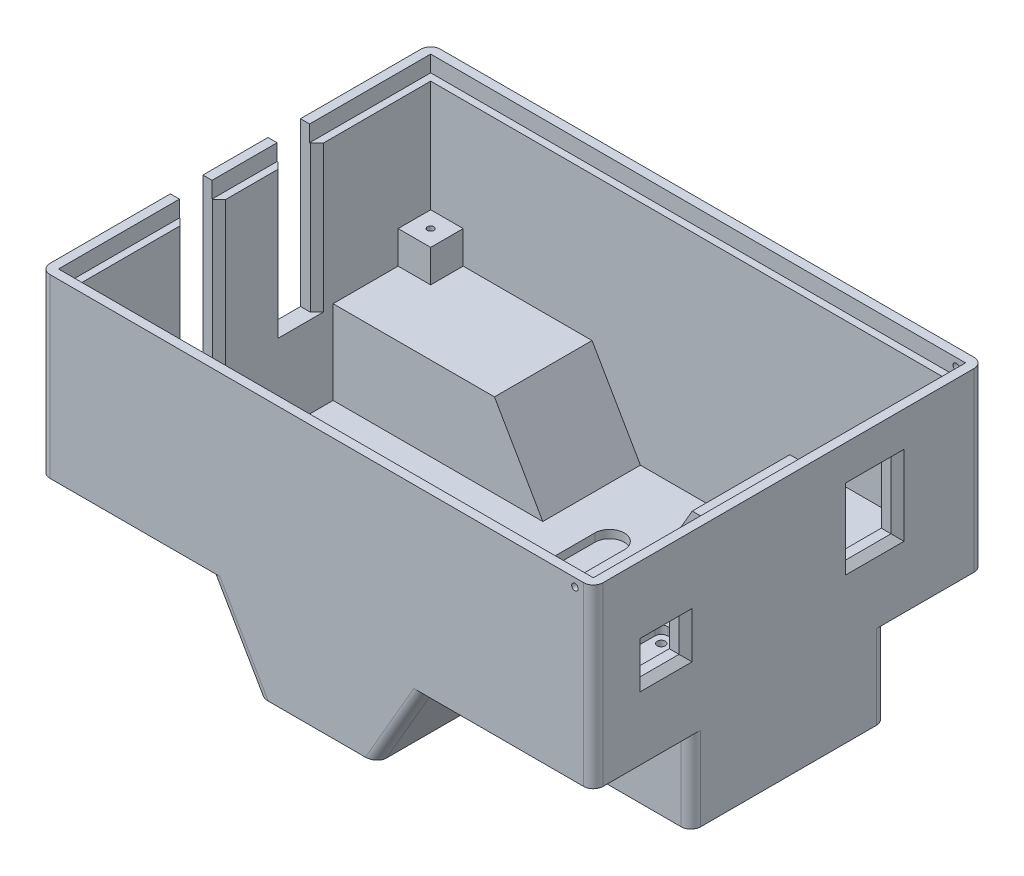
SolidWorks part; units mm, degrees
ref_plane "Plano frontal" through (0, 0, 0) normal (0, 0, 1) x (1, 0, 0)
ref_plane "Plano superior" through (0, 0, 0) normal (0, 1, 0) x (1, 0, 0)
ref_plane "Plano direito" through (0, 0, 0) normal (1, 0, 0) x (0, 0, -1)
sketch "Esboço7" plane through (0, 0, 0) normal (0, 1, 0) x (1, 0, 0)
  line L1 (85, -60) -> (-85, -60)
  line L2 (85, -60) -> (85, 60)
  line L3 (85, 60) -> (-85, 60)
  line L4 (-85, -60) -> (-85, 60)
  line L5 (85, -60) -> (-85, 60) construction
  line L6 (85, 60) -> (-85, -60) construction
  point P0 (0, 0)
  dimension "D1" = 120
  dimension "D2" = 170
extrude "Ressalto-extrusão4" add sketch "Esboço7" along normal blind 80 contours L4 L1 L2 L3 region at (0, 0, 0)
sketch "Esboço17" plane through (0, 0, 60) normal (0, 0, 1) x (1, 0, 0)
  line L0 (-85, 25.75) -> (-33.2819, 25.75)
  line L1 (-85, 80) -> (-85, 0) construction
  line L2 (-33.2819, 25.75) -> (-18.4152, 0)
  line L3 (85, 0) -> (-85, 0) construction
  line L4 (0, 0) -> (0, 80) construction
  line L5 (85, 80) -> (-85, 80) construction
  line L6 (-85, 25.75) -> (-85, 0)
  line L7 (-85, 0) -> (-18.4152, 0)
  line L8 (85, 0) -> (18.4152, 0)
  line L9 (85, 25.75) -> (85, 0)
  line L10 (85, 25.75) -> (33.2819, 25.75)
  line L11 (33.2819, 25.75) -> (18.4152, 0)
  line L12 (-53.5, 22.75) -> (-53.5, 25.75) construction
  line L13 (-18.4152, 0) -> (-21.4152, 0) construction
  circle A1 centre (-53.5, -11.25) radius 34
  circle A2 centre (-53.5, -11.25) radius 34 construction
  dimension "D3" = 3
  dimension "D1" = 60
  dimension "D4" = 3
  dimension "D2" = 0
extrude "Corte-extrusão9" cut sketch "Esboço17" against normal blind 30
mirror "Espelhar3" about plane through (0, 0, 0) normal (0, 0, 1) of "Corte-extrusão9"
shell "Casca1" thickness 5 removed face at (0, 80, 0)
sketch "Esboço9" plane through (0, 0, 0) normal (0, -1, 0) x (1, 0, 0)
  circle A16 centre (40.35, -13.25) radius 1.25 construction
  circle A17 centre (32.65, -13.25) radius 1.25 construction
  circle A18 centre (40.35, 13.25) radius 1.25 construction
  circle A19 centre (32.65, 13.25) radius 1.25 construction
  circle A20 centre (-30.15, 13.25) radius 1.25 construction
  circle A21 centre (-37.85, 13.25) radius 1.25 construction
  circle A22 centre (-30.15, -13.25) radius 1.25 construction
  circle A23 centre (-37.85, -13.25) radius 1.25 construction
  circle A24 centre (40.35, -13.25) radius 1.25
  circle A25 centre (32.65, -13.25) radius 1.25
  circle A26 centre (40.35, 13.25) radius 1.25
  circle A27 centre (32.65, 13.25) radius 1.25
  circle A28 centre (-30.15, 13.25) radius 1.25
  circle A29 centre (-37.85, 13.25) radius 1.25
  circle A30 centre (-30.15, -13.25) radius 1.25
  circle A31 centre (-37.85, -13.25) radius 1.25
extrude "Corte-extrusão4" cut sketch "Esboço9" against normal through all
sketch "Esboço10" plane through (0, 5, 0) normal (0, 1, 0) x (1, 0, 0)
  line L0 (0, 0) -> (36.5, 0) construction
  line L1 (40.35, -13.25) -> (32.65, 13.25) construction
  line L2 (41.35, 16.25) -> (31.65, 16.25)
  line L3 (43.35, 14.25) -> (43.35, -14.25)
  line L4 (41.35, -16.25) -> (31.65, -16.25)
  line L5 (29.65, 14.25) -> (29.65, -14.25)
  line L6 (43.35, 16.25) -> (29.65, -16.25) construction
  line L7 (43.35, -16.25) -> (29.65, 16.25) construction
  line L8 (0, 0) -> (0, -55) construction
  line L9 (15.5284, -55) -> (-15.5284, -55) construction
  line L10 (-30.15, 13.25) -> (-37.85, -13.25) construction
  line L12 (-38.85, 16.25) -> (-29.15, 16.25)
  line L13 (-40.85, 14.25) -> (-40.85, -14.25)
  line L14 (-38.85, -16.25) -> (-29.15, -16.25)
  line L15 (-27.15, 14.25) -> (-27.15, -14.25)
  line L16 (-40.85, 16.25) -> (-27.15, -16.25) construction
  line L17 (-40.85, -16.25) -> (-27.15, 16.25) construction
  arc A3 (-27.15, -14.25) -> (-29.15, -16.25) centre (-29.15, -14.25) cw
  arc A4 (-38.85, -16.25) -> (-40.85, -14.25) centre (-38.85, -14.25) cw
  arc A5 (-40.85, 14.25) -> (-38.85, 16.25) centre (-38.85, 14.25) cw
  arc A6 (-29.15, 16.25) -> (-27.15, 14.25) centre (-29.15, 14.25) cw
  arc A7 (43.35, -14.25) -> (41.35, -16.25) centre (41.35, -14.25) cw
  arc A8 (31.65, -16.25) -> (29.65, -14.25) centre (31.65, -14.25) cw
  arc A9 (29.65, 14.25) -> (31.65, 16.25) centre (31.65, 14.25) cw
  arc A10 (41.35, 16.25) -> (43.35, 14.25) centre (41.35, 14.25) cw
  point P4 (0, 0)
  point P13 (36.5, 0)
  point P25 (-34, 0)
  circle M37 centre (-30.15, -13.25) radius 1.25
  circle M38 centre (-37.85, -13.25) radius 1.25
  circle M39 centre (-30.15, 13.25) radius 1.25
  circle M40 centre (-37.85, 13.25) radius 1.25
  dimension "D3" = 2
  dimension "D1" = 3
  dimension "D2" = 3
extrude "Corte-extrusão5" cut sketch "Esboço10" against normal blind 2.5 contours L2 L5 L4 L3 | A6 L12 A5 L13 A4 L14 A3 L15 M37 M39 M40 M38 region at (36.5, 5, 0) region at (-34, 5, 0)
sketch "Esboço13" plane through (0, 80, 0) normal (0, 1, 0) x (1, 0, 0)
  circle A0 centre (0, 0) radius 4
  dimension "D1" = 8
extrude "Corte-extrusão7" cut sketch "Esboço13" against normal through all
sketch "Esboço14" plane through (0, 5, 0) normal (0, 1, 0) x (1, 0, 0)
  line L0 (0, -30) -> (0, 30) construction
  line L1 (-4.5, -30) -> (-4.5, 30)
  line L2 (4.5, -30) -> (4.5, 30)
  arc A0 (-4.5, -30) -> (4.5, -30) centre (0, -30) ccw
  arc A1 (4.5, 30) -> (-4.5, 30) centre (0, 30) ccw
  point P2 (0, 0)
  dimension "D1" = 60
  dimension "D2" = 9
extrude "Corte-extrusão8" cut sketch "Esboço14" against normal blind 2.5
sketch "Esboço22" plane through (80, 0, 0) normal (-1, 0, 0) x (0, 0, 1)
  line L0 (-33.5, 67.25) -> (-19.5, 67.25) construction
  line L4 (-33.5, 67.25) -> (-19.5, 67.25)
  line L5 (-33.5, 46.75) -> (-33.5, 67.25)
  line L6 (-19.5, 46.75) -> (-33.5, 46.75)
  line L7 (-19.5, 67.25) -> (-19.5, 46.75)
  line L8 (32.12, 57.45) -> (43.24, 57.45) construction
  line L9 (43.7, 56.89) -> (43.7, 47.24) construction
  line L10 (31.66, 47.24) -> (31.66, 56.89) construction
  line L11 (43.24, 47.24) -> (32.12, 47.24) construction
  line L12 (32.12, 57.45) -> (43.24, 57.45)
  line L13 (43.7, 56.89) -> (43.7, 47.24)
  line L14 (31.66, 47.24) -> (31.66, 56.89)
  line L15 (43.24, 47.24) -> (32.12, 47.24)
  line L16 (43.7, 56.89) -> (43.7, 57.45)
  line L17 (43.7, 57.45) -> (43.24, 57.45)
  line L19 (43.7, 57.45) -> (31.66, 57.45)
  line L20 (43.7, 57.45) -> (43.7, 47.24)
  line L21 (43.7, 47.24) -> (31.66, 47.24)
  line L22 (31.66, 57.45) -> (31.66, 47.24)
  line L23 (-33.5, 67.25) -> (-33.5, 46.75) construction
extrude "Corte-extrusão10" cut sketch "Esboço22" against normal through all contours L19 L22 L14 L21 L15 L13 L16 L17 L12 | L7 L4 L5 L6 region at (80, 57, -26.5) region at (80, 52.345, 37.68)
sketch "Esboço23" plane through (-80, 0, 0) normal (1, 0, 0) x (0, 0, -1)
  line L0 (0, 0) -> (0, 80) construction
  line L1 (-55, 80) -> (55, 80) construction
  line L2 (15, 0) -> (15, 80) construction
  line L3 (-15, 0) -> (-15, 80) construction
  line L5 (-20, 30) -> (-10, 30)
  line L6 (-20, 30) -> (-20, 80)
  line L7 (-20, 80) -> (-10, 80)
  line L8 (-10, 30) -> (-10, 80)
  line L9 (-20, 30) -> (-10, 80) construction
  line L10 (-20, 80) -> (-10, 30) construction
  line L11 (20, 30) -> (10, 30)
  line L12 (20, 30) -> (20, 80)
  line L13 (20, 80) -> (10, 80)
  line L14 (10, 30) -> (10, 80)
  line L15 (20, 30) -> (10, 80) construction
  line L16 (20, 80) -> (10, 30) construction
  point P9 (-15, 55)
  point P14 (15, 40)
  point P16 (15, 55)
  dimension "D1" = 15
  dimension "D3" = 10
  dimension "D4" = 50
  dimension "D2" = 15
extrude "Corte-extrusão11" cut sketch "Esboço23" against normal through all
chamfer "Chanfro1" distance 2 angle 45 4 edges at (-80, 55, 20) (-80, 55, -20) (-80, 55, -10) (-80, 55, 10)
ref_plane "Plano1" through (0, 70, 0) normal (0, 1, 0) x (1, 0, 0)
fillet "Filete2" radius 3 16 edges at (85, 12.875, 30) (85, 12.875, -30) (25.8485, 12.875, -30) (25.8485, 12.875, -60) (-25.8485, 12.875, -60) (-25.8485, 12.875, -30) (-85, 12.875, -30) (-85, 12.875, 30) (-25.8485, 12.875, 30) (25.8485, 12.875, 30) (25.8485, 12.875, 60) (-25.8485, 12.875, 60) (-85, 52.875, 60) (-85, 52.875, -60) (85, 52.875, -60) (85, 52.875, 60)
sketch "Esboço25" plane through (0, 80, 0) normal (0, 1, 0) x (1, 0, 0)
  line L0 (80, 55) -> (-80, 55) construction
  line L1 (82.2, -57.2) -> (-82.2, -57.2)
  line L2 (82.2, -57.2) -> (82.2, 57.2)
  line L3 (82.2, 57.2) -> (-82.2, 57.2)
  line L4 (-82.2, -57.2) -> (-82.2, 57.2)
  line L5 (82.2, -57.2) -> (-82.2, 57.2) construction
  line L6 (82.2, 57.2) -> (-82.2, -57.2) construction
  line L7 (-80, -55) -> (-80, -22) construction
  point P0 (0, 0)
  dimension "D1" = 2.2
  dimension "D2" = 2.2
extrude "Corte-extrusão12" cut sketch "Esboço25" against normal blind 5
sketch "Esboço26" plane through (0, 0, -60) normal (0, 0, -1) x (-1, 0, 0)
  circle A0 centre (-79.35, 77.5) radius 1 construction
  circle A1 centre (62.9655, 147.7282) radius 1 construction
  circle A2 centre (-79.35, 77.5) radius 1
  circle A3 centre (62.9655, 147.7282) radius 1
extrude "Corte-extrusão13" cut sketch "Esboço26" against normal through all
sketch "Esboço27" plane through (0, 30.75, 0) normal (0, 1, 0) x (1, 0, 0)
  line L1 (-70, 45) -> (-80, 45)
  line L2 (-70, 45) -> (-70, 55)
  line L3 (-70, 55) -> (-80, 55)
  line L4 (-80, 45) -> (-80, 55)
  line L5 (-70, 45) -> (-80, 55) construction
  line L6 (-70, 55) -> (-80, 45) construction
  line L7 (70, 45) -> (80, 45)
  line L8 (70, 45) -> (70, 55)
  line L9 (70, 55) -> (80, 55)
  line L10 (80, 45) -> (80, 55)
  line L11 (70, 45) -> (80, 55) construction
  line L12 (70, 55) -> (80, 45) construction
  line L13 (70, -45) -> (80, -45)
  line L14 (70, -45) -> (70, -55)
  line L15 (70, -55) -> (80, -55)
  line L16 (80, -45) -> (80, -55)
  line L17 (70, -45) -> (80, -55) construction
  line L18 (70, -55) -> (80, -45) construction
  line L19 (-70, -45) -> (-80, -45)
  line L20 (-70, -45) -> (-70, -55)
  line L21 (-70, -55) -> (-80, -55)
  line L22 (-80, -45) -> (-80, -55)
  line L23 (-70, -45) -> (-80, -55) construction
  line L24 (-70, -55) -> (-80, -45) construction
  circle A0 centre (-75, -50) radius 1 construction
  circle A1 centre (75, -50) radius 1 construction
  circle A2 centre (75, 50) radius 1 construction
  circle A3 centre (-75, 50) radius 1 construction
  circle A4 centre (-75, -50) radius 1 construction
  circle A5 centre (75, -50) radius 1 construction
  circle A6 centre (75, 50) radius 1 construction
  circle A7 centre (-75, 50) radius 1 construction
  circle A8 centre (75, -50) radius 1
  circle A9 centre (-75, -50) radius 1
  circle A10 centre (-75, 50) radius 1
  circle A11 centre (75, 50) radius 1
  dimension "D1" = 2
extrude "Ressalto-extrusão7" add sketch "Esboço27" along normal blind 10
chamfer "Chanfro2" distance 2 angle 45 8 edges at (85, 47.24, 37.68) (85, 52.345, 43.7) (85, 57.45, 37.68) (85, 52.345, 31.66) (85, 46.75, -26.5) (85, 57, -19.5) (85, 67.25, -26.5) (85, 57, -33.5)
